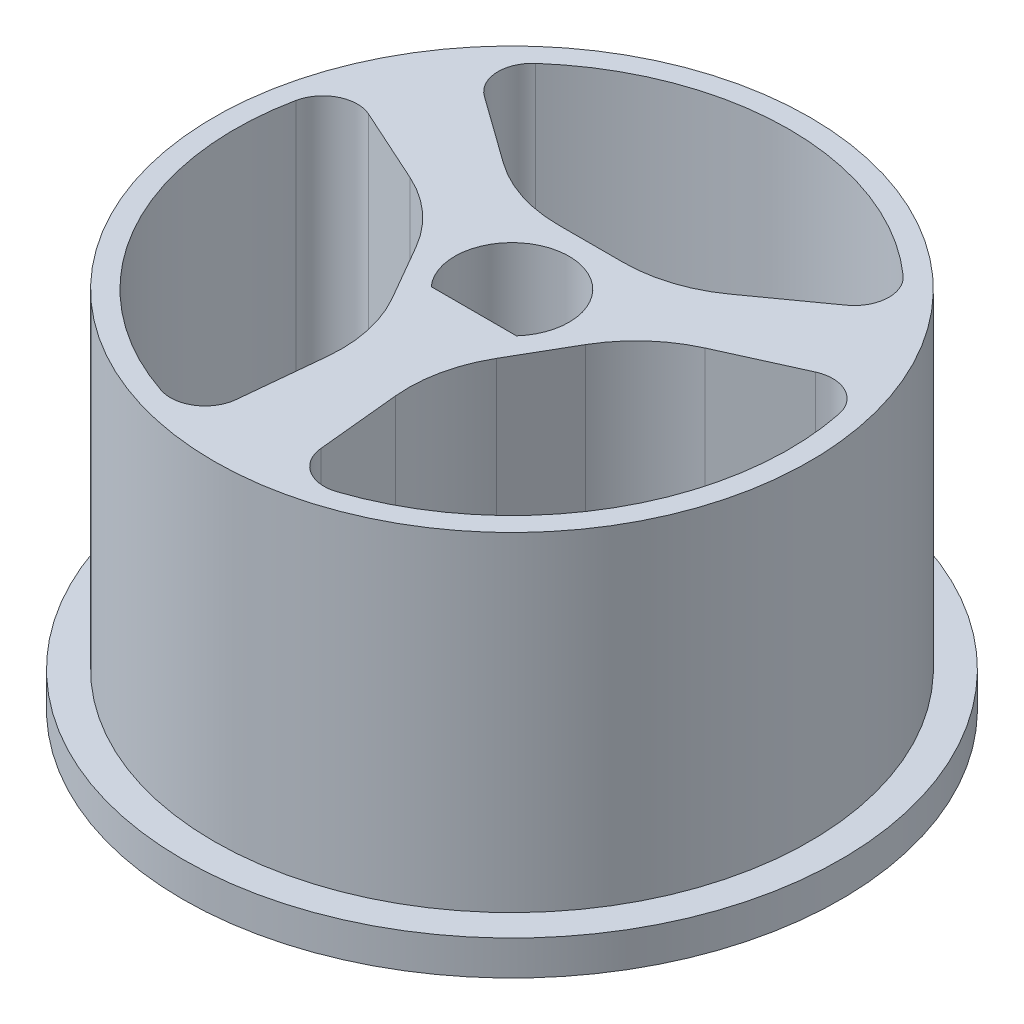
SolidWorks part; units mm, degrees
ref_plane "前视基准面" through (0, 0, 0) normal (0, 0, 1) x (1, 0, 0)
ref_plane "上视基准面" through (0, 0, 0) normal (0, 1, 0) x (1, 0, 0)
ref_plane "右视基准面" through (0, 0, 0) normal (1, 0, 0) x (0, 0, -1)
sketch "草图1" plane through (0, 0, 0) normal (0, 1, 0) x (1, 0, 0)
  line L0 (-1.2298, -1.1) -> (1.2298, -1.1)
  line L1 (-2.4425, -0.3243) -> (-1.5021, -1.9531)
  line L4 (4.2575, 1.3199) -> (6.4464, 2.3104)
  line L5 (3.2718, 3.0272) -> (5.2241, 4.4276)
  line L8 (-0.9857, -4.3471) -> (-1.2223, -6.738)
  line L9 (0.9857, -4.3471) -> (1.2223, -6.738)
  line L10 (0.9403, 2.2774) -> (-0.9403, 2.2774)
  line L11 (1.5021, -1.9531) -> (2.4425, -0.3243)
  line L12 (-3.2718, 3.0272) -> (-5.2241, 4.4276)
  line L13 (-4.2575, 1.3199) -> (-6.4464, 2.3104)
  arc A0 (1.2298, -1.1) -> (-1.2298, -1.1) centre (0, 0) ccw
  circle A1 centre (0, 0) radius 8.6
  circle A2 centre (0, 0) radius 9.5
  arc A3 (-7.8385, 1.5993) -> (-2.5343, -7.588) centre (0, 0) ccw
  arc A4 (-2.5343, 7.588) -> (-5.3043, 5.9887) centre (0, 0) ccw
  arc A5 (5.3043, 5.9887) -> (-5.3043, 5.9887) centre (0, 0) ccw
  arc A6 (2.5343, -7.588) -> (7.8385, 1.5993) centre (0, 0) ccw
  arc A9 (6.4464, 2.3104) -> (7.8385, 1.5993) centre (6.8587, 1.3993) cw
  arc A10 (5.2241, 4.4276) -> (5.3043, 5.9887) centre (4.6412, 5.2401) ccw
  arc A17 (-1.2223, -6.738) -> (-2.5343, -7.588) centre (-2.2175, -6.6395) cw
  arc A18 (1.2223, -6.738) -> (2.5343, -7.588) centre (2.2175, -6.6395) ccw
  arc A20 (-0.9857, -4.3471) -> (-1.5021, -1.9531) centre (-4.9662, -3.9531) ccw
  arc A21 (-4.2575, 1.3199) -> (-2.4425, -0.3243) centre (-5.9066, -2.3243) cw
  arc A22 (-3.2718, 3.0272) -> (-0.9403, 2.2774) centre (-0.9403, 6.2774) ccw
  arc A23 (3.2718, 3.0272) -> (0.9403, 2.2774) centre (0.9403, 6.2774) cw
  arc A24 (4.2575, 1.3199) -> (2.4425, -0.3243) centre (5.9066, -2.3243) ccw
  arc A25 (-5.2241, 4.4276) -> (-5.3043, 5.9887) centre (-4.6412, 5.2401) cw
  arc A26 (-6.4464, 2.3104) -> (-7.8385, 1.5993) centre (-6.8587, 1.3993) ccw
  arc A27 (0.9857, -4.3471) -> (1.5021, -1.9531) centre (4.9662, -3.9531) cw
  arc A29 (-7.8385, 1.5993) -> (-7.8385, -1.5993) centre (0, 0) ccw
  arc A30 (5.3043, 5.9887) -> (2.5343, 7.588) centre (0, 0) ccw
  arc A31 (7.8385, -1.5993) -> (7.8385, 1.5993) centre (0, 0) ccw
  arc A32 (2.5343, -7.588) -> (5.3043, -5.9887) centre (0, 0) ccw
  arc A33 (-5.3043, -5.9887) -> (-2.5343, -7.588) centre (0, 0) ccw
  point P14 (0.7902, 2.3718)
  point P17 (-0.7902, 2.3718)
  point P20 (-1.3361, 7.8876)
  point P23 (1.3361, 7.8876)
  point P79 (0, 0)
  point P87 (0, 0)
  dimension "D1" = 3.3
  dimension "D3" = 17.2
  dimension "D6" = 4
  dimension "D2" = 1.1
  dimension "D7" = 3
extrude "凸台-拉伸2" add sketch "草图1" along normal blind 1 contours A2 A1 region at (-9.2313, 0, 0)
extrude "凸台-拉伸4" add sketch "草图1<4>" along normal blind 10.5 contours A1 A33 L8 A17 A32 A18 L9 A31 L4 A9 A30 A10 L5 A29 A26 L13 L12 A25 A4 A0 region at (-8.3568, 0, 0)
sketch "草图1<4>" plane through (0, 0, 0) normal (0, 1, 0) x (1, 0, 0) same geometry as "草图1"
